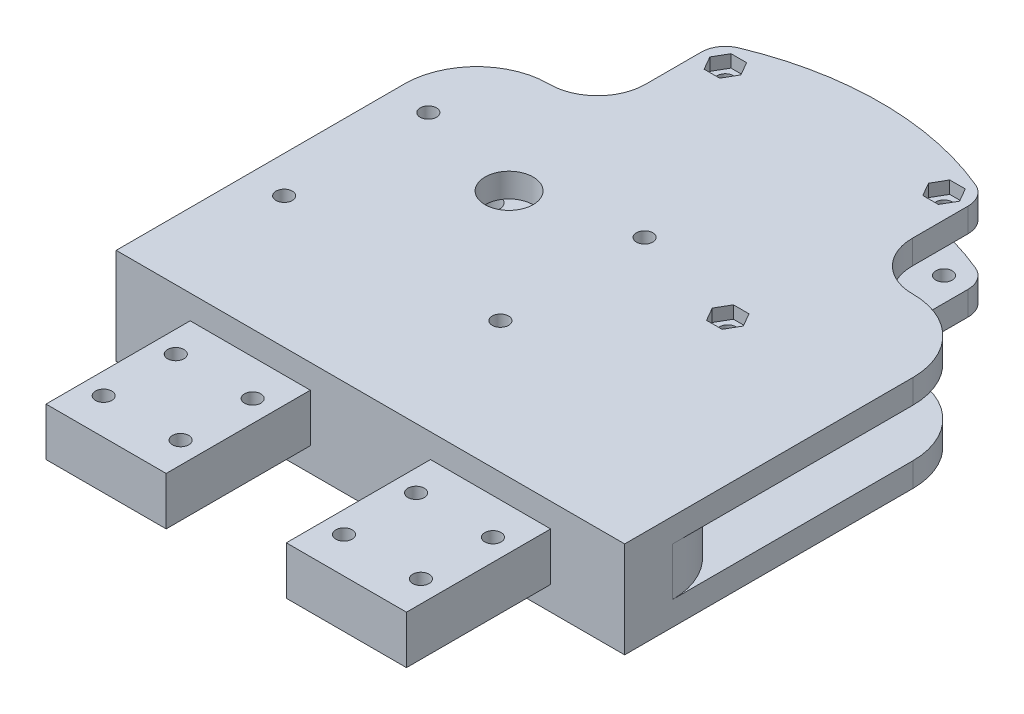
SolidWorks part; units mm, degrees
ref_plane "Front Plane" through (0, 0, 0) normal (0, 0, 1) x (1, 0, 0)
ref_plane "Top Plane" through (0, 0, 0) normal (0, 1, 0) x (1, 0, 0)
ref_plane "Right Plane" through (0, 0, 0) normal (1, 0, 0) x (0, 0, -1)
sketch "Sketch1" plane through (0, 0, 0) normal (0, 1, 0) x (1, 0, 0)
  line L0 (0, -32.7) -> (0, 32.7) construction
  line L1 (15.15, -32.7) -> (-15.15, -32.7)
  line L2 (30.15, -17.7) -> (30.15, 17.7)
  line L3 (15.15, 32.7) -> (-15.15, 32.7)
  line L4 (-30.15, -17.7) -> (-30.15, 17.7)
  line L5 (30.15, -32.7) -> (-30.15, 32.7) construction
  line L6 (30.15, 32.7) -> (-30.15, -32.7) construction
  line L7 (30.15, 0) -> (-30.15, 0) construction
  line L8 (-15, 20) -> (-15, -20) construction
  line L9 (-22.5, -15) -> (-22.5, 15) construction
  line L10 (0, 19.4) -> (0, -16.9) construction
  line L12 (-9, 4.7163) -> (-9, -16.9)
  line L13 (-9, -16.9) -> (9, -16.9)
  line L14 (9, 4.7163) -> (9, -16.9)
  line L15 (-9, 4.7163) -> (9, -16.9) construction
  line L16 (-9, -16.9) -> (9, 4.7163) construction
  line L17 (-15, 20) -> (15, 20) construction
  circle A0 centre (-15, 20) radius 2.3
  circle A1 centre (-25, 0) radius 2.3
  circle A2 centre (-15, -20) radius 2.3
  circle A3 centre (-22.5, 15) radius 1.7
  circle A4 centre (-22.5, -15) radius 1.7
  circle A5 centre (15, -20) radius 2.3
  circle A6 centre (22.5, -15) radius 1.7
  circle A7 centre (25, 0) radius 2.3
  circle A8 centre (22.5, 15) radius 1.7
  circle A9 centre (15, 20) radius 2.3
  arc A10 (9, 4.7163) -> (-9, 4.7163) centre (0, 9.3) ccw
  arc A11 (15.15, -32.7) -> (30.15, -17.7) centre (15.15, -17.7) ccw
  arc A12 (30.15, 17.7) -> (15.15, 32.7) centre (15.15, 17.7) ccw
  arc A13 (-15.15, 32.7) -> (-30.15, 17.7) centre (-15.15, 17.7) ccw
  arc A14 (-15.15, -32.7) -> (-30.15, -17.7) centre (-15.15, -17.7) cw
  point P0 (0, 0)
  point P20 (0, -6.0918)
  point P21 (-22.5, 0)
  point P23 (-15, 0)
  point P40 (0, -16.9)
  dimension "D3" = 4.6
  dimension "D4" = 4.6
  dimension "D5" = 4.6
  dimension "D6" = 3.4
  dimension "D7" = 3.4
  dimension "D13" = 20.2
  dimension "D17" = 15
  dimension "D1" = 60.3
  dimension "D2" = 65.4
  dimension "D8" = 15
  dimension "D9" = 22.5
  dimension "D10" = 25
  dimension "D11" = 15
  dimension "D12" = 20
  dimension "D14" = 36.3
  dimension "D15" = 18
  dimension "D16" = 0.6
extrude "Boss-Extrude2" add sketch "Sketch1" along normal blind 5
sketch "Sketch2" plane through (0, 5, 0) normal (0, 1, 0) x (1, 0, 0)
  line L0 (0, 9.3) -> (45.5, 9.3) construction
  line L1 (45.5, 9.3) -> (45.5, 54.3) construction
  line L2 (45.5, 54.3) -> (0, 54.3) construction
  line L3 (0, 54.3) -> (0, 9.3) construction
  line L4 (0, 0) -> (45.5, 0) construction
  line L5 (15.15, 32.7) -> (-15.15, 32.7) construction
  line L6 (60.65, -32.7) -> (15.35, -32.7)
  line L7 (75.65, -17.7) -> (75.65, 17.7)
  line L8 (60.65, 32.7) -> (50.5, 32.7)
  line L10 (75.65, -32.7) -> (15.35, 32.7) construction
  line L11 (75.65, 32.7) -> (15.35, -32.7) construction
  line L12 (-5, 32.7) -> (15.35, 32.7)
  line L13 (15.35, 32.7) -> (28.35, 18.6005)
  line L14 (28.35, 18.6005) -> (28.35, -18.6005)
  line L15 (-5, 54.3) -> (-5, 32.7)
  line L16 (50.5, 54.3) -> (50.5, 32.7)
  line L17 (28.35, -18.6005) -> (15.35, -32.7)
  circle A0 centre (45.5, 9.3) radius 1.7
  circle A1 centre (45.5, 54.3) radius 1.7
  circle A2 centre (0, 54.3) radius 1.7
  arc A4 (-1.9321, 58.9116) -> (-5, 54.3) centre (0, 54.3) ccw
  arc A5 (50.5, 54.3) -> (47.4321, 58.9116) centre (45.5, 54.3) ccw
  arc A6 (-1.9321, 58.9116) -> (47.4321, 58.9116) centre (22.75, 0) cw
  arc A7 (75.65, 17.7) -> (60.65, 32.7) centre (60.65, 17.7) ccw
  arc A8 (60.65, -32.7) -> (75.65, -17.7) centre (60.65, -17.7) ccw
  dimension "D2" = 3.4
  dimension "D4" = 3.4
  dimension "D5" = 3.4
  dimension "D6" = 65.4
  dimension "D7" = 10
  dimension "D8" = 10
  dimension "D12" = 15
  dimension "D1" = 45.5
  dimension "D3" = 45
  dimension "D9" = 60.3
  dimension "D10" = 13
  dimension "D11" = 37.201
extrude "Boss-Extrude4" add sketch "Sketch2" against normal blind 5
sketch "Sketch4" plane through (0, 5, 0) normal (0, 1, 0) x (1, 0, 0)
  line L0 (-30.15, -17.7) -> (-15.15, -32.7)
  line L1 (-15.15, -32.7) -> (60.65, -32.7)
  line L2 (60.65, -32.7) -> (75.65, -17.7)
  line L3 (75.65, -17.7) -> (75.65, -42.3)
  line L4 (75.65, -42.3) -> (-30.15, -42.3)
  line L5 (-30.15, -42.3) -> (-30.15, -17.7)
  line L6 (-9, -17.3) -> (8.6243, -17.3) construction
  line L7 (-9, -16.9) -> (9, -16.9) construction
  point P14 (-0.1879, -17.3)
  dimension "D1" = 0.4
  dimension "D2" = 25
extrude "Boss-Extrude7" add sketch "Sketch4" against normal blind 5
sketch "Sketch5" plane through (0, 5, 0) normal (0, 1, 0) x (1, 0, 0)
  line L0 (75.65, -42.3) -> (75.65, 17.7) construction
  line L1 (-30.15, -42.3) -> (75.65, -42.3)
  line L2 (-30.15, -42.3) -> (-30.15, -32.3)
  line L3 (-15.15, -17.3) -> (60.65, -17.3)
  line L4 (75.65, -42.3) -> (75.65, -32.3)
  arc A0 (60.65, -17.3) -> (75.65, -32.3) centre (60.65, -32.3) cw
  arc A1 (-30.15, -32.3) -> (-15.15, -17.3) centre (-15.15, -32.3) cw
  point P9 (75.65, -17.3)
  dimension "D2" = 15
  dimension "D1" = 25
extrude "Boss-Extrude8" add sketch "Sketch5" along normal blind 10
sketch "Sketch6" plane through (0, 15, 0) normal (0, 1, 0) x (1, 0, 0)
  line L0 (-30.15, -42.3) -> (-30.15, 17.7)
  line L1 (-15.15, 32.7) -> (-5, 32.7)
  line L2 (-5, 32.7) -> (-5, 54.3)
  line L3 (50.5, 54.3) -> (50.5, 32.7)
  line L4 (50.5, 32.7) -> (60.65, 32.7)
  line L5 (75.65, 17.7) -> (75.65, -42.3)
  line L6 (75.65, -42.3) -> (-30.15, -42.3)
  arc A0 (-5, 54.3) -> (-1.9321, 58.9116) centre (0, 54.3) cw
  arc A1 (50.5, 54.3) -> (47.4321, 58.9116) centre (45.5, 54.3) ccw
  arc A2 (-1.9321, 58.9116) -> (47.4321, 58.9116) centre (22.75, 0) cw
  arc A3 (47.4321, 58.9116) -> (-1.9321, 58.9116) centre (22.75, 0) ccw construction
  arc A4 (60.65, 32.7) -> (75.65, 17.7) centre (60.65, 17.7) cw
  arc A5 (-30.15, 17.7) -> (-15.15, 32.7) centre (-15.15, 17.7) cw
  circle A6 centre (-22.5, 15) radius 1.7
  circle A7 centre (-22.5, -15) radius 1.7
  circle A8 centre (22.5, -15) radius 1.7
  circle A9 centre (22.5, 15) radius 1.7
  circle A10 centre (45.5, 9.3) radius 1.7
  circle A11 centre (0, 9.3) radius 5
  circle A12 centre (45.5, 54.3) radius 1.7
  circle A13 centre (0, 54.3) radius 1.7
  point P26 (75.65, 32.7)
  point P29 (-30.15, 32.7)
  dimension "D1" = 15
  dimension "D2" = 3.4
  dimension "D3" = 3.4
  dimension "D4" = 3.4
  dimension "D5" = 3.4
  dimension "D6" = 3.4
  dimension "D7" = 3.4
  dimension "D8" = 3.4
  dimension "D9" = 10
extrude "Boss-Extrude9" add sketch "Sketch6" along normal blind 5
sketch "Sketch7" plane through (0, 0, 42.3) normal (0, 0, 1) x (1, 0, 0)
  line L0 (22.75, 0) -> (22.75, 20) construction
  line L1 (-7.25, 15) -> (2.75, 15)
  line L2 (-7.25, 15) -> (-7.25, 5)
  line L3 (-7.25, 5) -> (2.75, 5)
  line L4 (2.75, 15) -> (2.75, 5)
  line L5 (52.75, 15) -> (42.75, 15)
  line L6 (52.75, 15) -> (52.75, 5)
  line L7 (52.75, 5) -> (42.75, 5)
  line L8 (42.75, 15) -> (42.75, 5)
  line L9 (-30.15, 0) -> (75.65, 0) construction
  line L10 (-30.15, 20) -> (75.65, 20) construction
  line L11 (2.75, 15) -> (42.75, 15) construction
  point P11 (22.75, 15)
  dimension "D1" = 10
  dimension "D2" = 10
  dimension "D3" = 40
  dimension "D4" = 10
  dimension "D5" = 10
  dimension "D6" = 5
extrude "Boss-Extrude10" add sketch "Sketch7" along normal blind 30
sketch "Sketch9" plane through (0, 15, 0) normal (0, 1, 0) x (1, 0, 0)
  line L0 (-7.25, -72.3) -> (-7.25, -42.3) construction
  line L1 (52.75, -42.3) -> (52.75, -72.3) construction
  line L2 (42.75, -72.3) -> (42.75, -42.3) construction
  line L3 (-30.15, -42.3) -> (75.65, -42.3) construction
  line L4 (-7.25, -72.3) -> (-14.75, -72.3)
  line L5 (-7.25, -72.3) -> (-7.25, -42.3)
  line L6 (-7.25, -42.3) -> (-14.75, -42.3)
  line L7 (-14.75, -72.3) -> (-14.75, -42.3)
  line L8 (-2.25, -42.3) -> (-2.25, -72.3) construction
  line L9 (2.75, -42.3) -> (10.25, -42.3)
  line L10 (2.75, -42.3) -> (2.75, -72.3)
  line L11 (2.75, -72.3) -> (10.25, -72.3)
  line L12 (10.25, -42.3) -> (10.25, -72.3)
  line L13 (42.75, -72.3) -> (35.25, -72.3)
  line L14 (42.75, -72.3) -> (42.75, -42.3)
  line L15 (42.75, -42.3) -> (35.25, -42.3)
  line L16 (35.25, -72.3) -> (35.25, -42.3)
  line L17 (52.75, -72.3) -> (60.25, -72.3)
  line L18 (52.75, -72.3) -> (52.75, -42.3)
  line L19 (52.75, -42.3) -> (60.25, -42.3)
  line L20 (60.25, -72.3) -> (60.25, -42.3)
  line L21 (2.75, -42.3) -> (-7.25, -42.3) construction
  line L22 (2.75, -72.3) -> (-7.25, -72.3) construction
  line L23 (22.75, -42.3) -> (22.75, -72.3) construction
  line L27 (-14.75, -57.3) -> (60.25, -57.3) construction
  circle A0 centre (-10.25, -49.8) radius 1.7
  circle A1 centre (-10.25, -64.8) radius 1.7
  circle A2 centre (5.75, -64.8) radius 1.7
  circle A3 centre (5.75, -49.8) radius 1.7
  circle A4 centre (39.75, -64.8) radius 1.7
  circle A5 centre (39.75, -49.8) radius 1.7
  circle A6 centre (55.75, -64.8) radius 1.7
  circle A7 centre (55.75, -49.8) radius 1.7
  dimension "D6" = 3.4
  dimension "D1" = 7.5
  dimension "D2" = 7.5
  dimension "D3" = 7.5
  dimension "D4" = 7.5
  dimension "D5" = 3
  dimension "D7" = 7.5
extrude "Boss-Extrude11" add sketch "Sketch9" against normal blind 10
fillet "Fillet1" radius 10 4 edges at (50.5, 17.5, -32.7) (50.5, 2.5, -32.7) (-5, 17.5, -32.7) (-5, 2.5, -32.7)
sketch "Sketch10" plane through (0, 5, 0) normal (0, 1, 0) x (1, 0, 0)
  line L0 (0, 0) -> (0, -22.5693) construction
  line L1 (-19.2668, 15) -> (-20.8834, 17.8)
  line L2 (-20.8834, 17.8) -> (-24.1166, 17.8)
  line L3 (-24.1166, 17.8) -> (-25.7332, 15)
  line L4 (-25.7332, 15) -> (-24.1166, 12.2)
  line L5 (-24.1166, 12.2) -> (-20.8834, 12.2)
  line L6 (-20.8834, 12.2) -> (-19.2668, 15)
  line L7 (0, 0) -> (-12.1994, 0) construction
  line L8 (-25.7332, -15) -> (-24.1166, -12.2)
  line L9 (-24.1166, -17.8) -> (-25.7332, -15)
  line L10 (-20.8834, -17.8) -> (-24.1166, -17.8)
  line L11 (-19.2668, -15) -> (-20.8834, -17.8)
  line L12 (-20.8834, -12.2) -> (-19.2668, -15)
  line L13 (-24.1166, -12.2) -> (-20.8834, -12.2)
  line L14 (24.1166, -12.2) -> (20.8834, -12.2)
  line L15 (20.8834, -12.2) -> (19.2668, -15)
  line L16 (19.2668, -15) -> (20.8834, -17.8)
  line L17 (20.8834, -17.8) -> (24.1166, -17.8)
  line L18 (24.1166, -17.8) -> (25.7332, -15)
  line L19 (25.7332, -15) -> (24.1166, -12.2)
  line L20 (20.8834, 12.2) -> (19.2668, 15)
  line L21 (24.1166, 12.2) -> (20.8834, 12.2)
  line L22 (25.7332, 15) -> (24.1166, 12.2)
  line L23 (24.1166, 17.8) -> (25.7332, 15)
  line L24 (20.8834, 17.8) -> (24.1166, 17.8)
  line L25 (19.2668, 15) -> (20.8834, 17.8)
  circle A0 centre (-22.5, 15) radius 2.8 construction
  dimension "D1" = 5.6
  dimension "D2" = 2.8
extrude "Cut-Extrude1" cut sketch "Sketch10" against normal blind 2.6 and the other way blind 2.7
sketch "Sketch11" plane through (0, 15, 0) normal (0, -1, 0) x (1, 0, 0)
  line L1 (-19.2668, 15) -> (-20.8834, 17.8)
  line L2 (-20.8834, 17.8) -> (-24.1166, 17.8)
  line L3 (-24.1166, 17.8) -> (-25.7332, 15)
  line L4 (-25.7332, 15) -> (-24.1166, 12.2)
  line L5 (-24.1166, 12.2) -> (-20.8834, 12.2)
  line L6 (-20.8834, 12.2) -> (-19.2668, 15)
  line L7 (0, 0) -> (-12.8954, 0) construction
  line L8 (0, 0) -> (0, 13.9475) construction
  line L9 (-20.8834, -12.2) -> (-19.2668, -15)
  line L10 (-24.1166, -12.2) -> (-20.8834, -12.2)
  line L11 (-25.7332, -15) -> (-24.1166, -12.2)
  line L12 (-24.1166, -17.8) -> (-25.7332, -15)
  line L13 (-20.8834, -17.8) -> (-24.1166, -17.8)
  line L14 (-19.2668, -15) -> (-20.8834, -17.8)
  line L15 (19.2668, -15) -> (20.8834, -17.8)
  line L16 (20.8834, -17.8) -> (24.1166, -17.8)
  line L17 (24.1166, -17.8) -> (25.7332, -15)
  line L18 (25.7332, -15) -> (24.1166, -12.2)
  line L19 (24.1166, -12.2) -> (20.8834, -12.2)
  line L20 (20.8834, -12.2) -> (19.2668, -15)
  line L21 (20.8834, 12.2) -> (19.2668, 15)
  line L22 (24.1166, 12.2) -> (20.8834, 12.2)
  line L23 (25.7332, 15) -> (24.1166, 12.2)
  line L24 (24.1166, 17.8) -> (25.7332, 15)
  line L25 (20.8834, 17.8) -> (24.1166, 17.8)
  line L26 (19.2668, 15) -> (20.8834, 17.8)
  circle A0 centre (-22.5, 15) radius 2.8 construction
  dimension "D1" = 5.6
  dimension "D2" = 2.8
extrude "Cut-Extrude2" cut sketch "Sketch11" against normal blind 2.6 and the other way blind 2.7
sketch "Sketch13" plane through (0, 20, 0) normal (0, 1, 0) x (1, 0, 0)
  line L1 (3.2332, 54.3) -> (1.6166, 57.1)
  line L2 (1.6166, 57.1) -> (-1.6166, 57.1)
  line L3 (-1.6166, 57.1) -> (-3.2332, 54.3)
  line L4 (-3.2332, 54.3) -> (-1.6166, 51.5)
  line L5 (-1.6166, 51.5) -> (1.6166, 51.5)
  line L6 (1.6166, 51.5) -> (3.2332, 54.3)
  line L7 (48.7332, 54.3) -> (47.1166, 57.1)
  line L8 (47.1166, 57.1) -> (43.8834, 57.1)
  line L9 (43.8834, 57.1) -> (42.2668, 54.3)
  line L10 (42.2668, 54.3) -> (43.8834, 51.5)
  line L11 (43.8834, 51.5) -> (47.1166, 51.5)
  line L12 (47.1166, 51.5) -> (48.7332, 54.3)
  line L13 (48.7332, 9.3) -> (47.1166, 12.1)
  line L14 (47.1166, 12.1) -> (43.8834, 12.1)
  line L15 (43.8834, 12.1) -> (42.2668, 9.3)
  line L16 (42.2668, 9.3) -> (43.8834, 6.5)
  line L17 (43.8834, 6.5) -> (47.1166, 6.5)
  line L18 (47.1166, 6.5) -> (48.7332, 9.3)
  circle A0 centre (0, 54.3) radius 2.8 construction
  circle A1 centre (45.5, 54.3) radius 2.8 construction
  circle A2 centre (45.5, 9.3) radius 2.8 construction
  dimension "D1" = 5.6
  dimension "D2" = 2.8
  dimension "D3" = 5.6
  dimension "D4" = 2.8
  dimension "D5" = 5.6
  dimension "D6" = 2.8
extrude "Cut-Extrude4" cut sketch "Sketch13" against normal blind 2.6
sketch "Sketch14" plane through (0, 5, 0) normal (0, 1, 0) x (1, 0, 0)
  line L0 (22.75, 58.8732) -> (22.75, 33.8732) construction
  line L1 (27.75, 58.8732) -> (27.75, 33.8732)
  line L2 (17.75, 58.8732) -> (17.75, 33.8732)
  arc A1 (27.75, 58.8732) -> (17.75, 58.8732) centre (22.75, 58.8732) ccw
  arc A2 (17.75, 33.8732) -> (27.75, 33.8732) centre (22.75, 33.8732) ccw
  arc A3 (47.4321, 58.9116) -> (-1.9321, 58.9116) centre (22.75, 0) ccw construction
  point P6 (22.75, 46.3732)
  dimension "D2" = 5
  dimension "D3" = 25
extrude "Boss-Extrude12" add sketch "Sketch14" along normal blind 10
